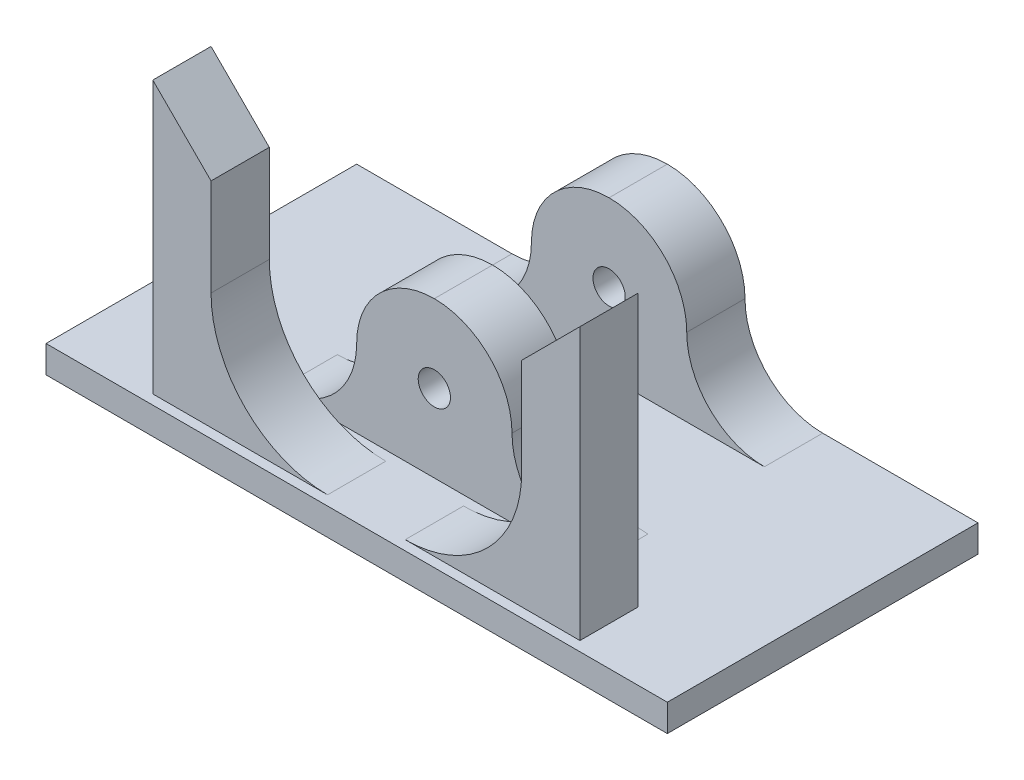
SolidWorks part; units mm, degrees
material "ABS PC"
ref_plane "Front Plane" through (0, 0, 0) normal (0, 0, 1) x (1, 0, 0)
ref_plane "Top Plane" through (0, 0, 0) normal (0, 1, 0) x (1, 0, 0)
ref_plane "Right Plane" through (0, 0, 0) normal (1, 0, 0) x (0, 0, -1)
sketch "Sketch1" plane through (0, 0, 0) normal (0, 1, 0) x (1, 0, 0)
  line L1 (0, 0) -> (-160, 0)
  line L2 (0, 0) -> (0, 60)
  line L3 (0, 60) -> (-160, 60)
  line L4 (-160, 0) -> (-160, 60)
  dimension "D1" = 160
  dimension "D2" = 60
extrude "Boss-Extrude1" add sketch "Sketch1" along normal blind 7
sketch "Sketch2" plane through (0, 7, 0) normal (0, 1, 0) x (1, 0, 0)
  line L0 (0, 60) -> (-160, 60) construction
  line L1 (-100, 60) -> (-60, 60)
  line L2 (-100, 60) -> (-100, 0)
  line L3 (-100, 0) -> (-60, 0)
  line L4 (-60, 60) -> (-60, 0)
  line L5 (-160, 0) -> (0, 0) construction
  line L6 (-160, 0) -> (0, 0) construction
  point P10 (-80, 0)
  point P11 (-80, 0)
  dimension "D1" = 40
extrude "Boss-Extrude2" add sketch "Sketch2" along normal blind 40
fillet "Fillet1" radius 20 2 edges at (-60, 47, -30) (-100, 47, -30)
sketch "Sketch3" plane through (-60, 0, 0) normal (1, 0, 0) x (0, 0, -1)
  line L0 (0, 7) -> (60, 7) construction
  line L1 (15, 7) -> (45, 7)
  line L2 (15, 7) -> (15, 47)
  line L3 (15, 47) -> (45, 47)
  line L4 (45, 7) -> (45, 47)
  point P6 (30, 7)
  point P7 (30, 47)
  dimension "D1" = 30
  dimension "D2" = 40
extrude "Cut-Extrude1" cut sketch "Sketch3" against normal blind 40
sketch "Sketch4" plane through (0, 0, 0) normal (0, 0, 1) x (1, 0, 0)
  circle A0 centre (-80, 27) radius 4.15
  arc A1 (-80, 47) -> (-100, 27) centre (-80, 27) ccw construction
  dimension "D1" = 8.3
extrude "Cut-Extrude2" cut sketch "Sketch4" against normal through all
fillet "Fillet2" radius 20 4 edges at (-100, 7, -7.5) (-100, 7, -52.5) (-60, 7, -7.5) (-60, 7, -52.5)
sketch "Sketch5" plane through (0, 0, 0) normal (0, 0, 1) x (1, 0, 0)
  line L1 (-160, 7) -> (0, 7)
  line L2 (-160, 7) -> (-160, 0)
  line L3 (-160, 0) -> (0, 0)
  line L4 (0, 7) -> (0, 0)
extrude "Boss-Extrude3" add sketch "Sketch5" along normal blind 20
sketch "Sketch6" plane through (0, 7, 0) normal (0, 1, 0) x (1, 0, 0)
  line L0 (-80, -20) -> (-80, 111.1387) construction
  line L6 (0, -20) -> (0, 60) construction
  line L7 (0, -20) -> (-160, -20) construction
  line L8 (-135, -2.5) -> (-120, -2.5)
  line L9 (-135, -2.5) -> (-135, -17.5)
  line L10 (-135, -17.5) -> (-120, -17.5)
  line L11 (-120, -2.5) -> (-120, -17.5)
  line L12 (-25, -17.5) -> (-40, -17.5)
  line L13 (-40, -2.5) -> (-40, -17.5)
  line L14 (-25, -2.5) -> (-40, -2.5)
  line L15 (-25, -2.5) -> (-25, -17.5)
  dimension "D1" = 80
  dimension "D2" = 15
  dimension "D3" = 15
  dimension "D4" = 2.5
  dimension "D5" = 40
extrude "Boss-Extrude4" add sketch "Sketch6" along normal blind 70
fillet "Fillet3" radius 30 2 edges at (-40, 7, 10) (-120, 7, 10)
chamfer "Chamfer1" distance 15 angle 45 2 edges at (-40, 77, 10) (-120, 77, 10)
equation "\"dowel hole\"= 8.3mm"
equation "\"D1@Sketch4\"=\"dowel hole\""
